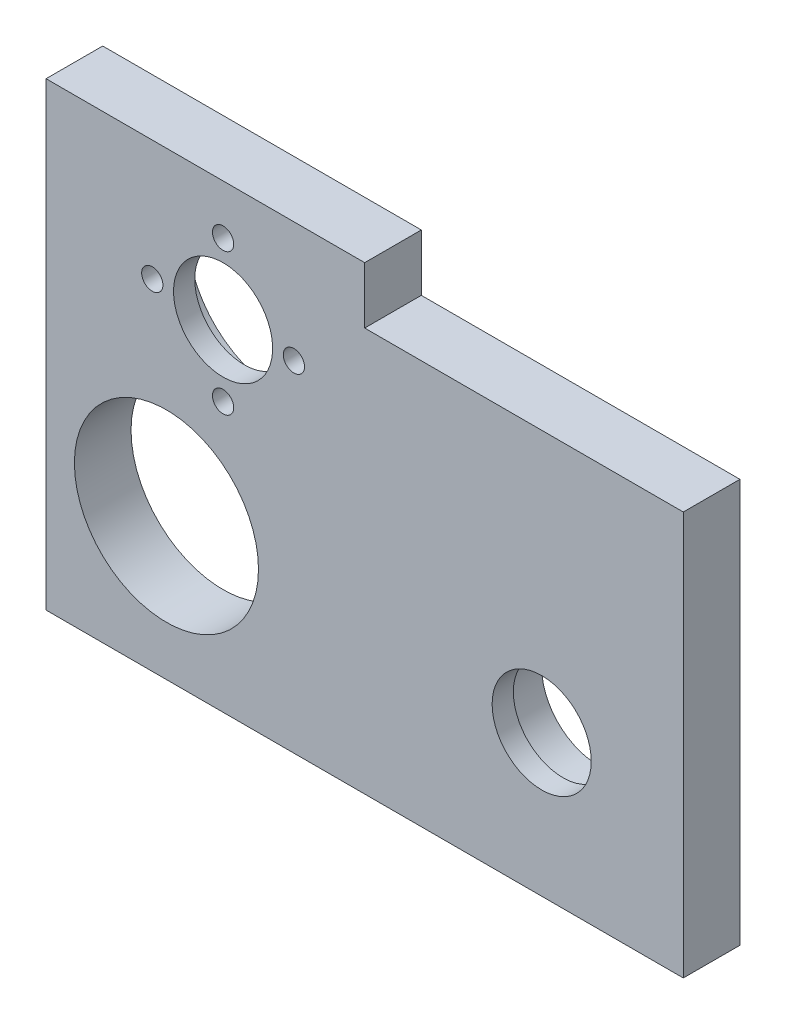
SolidWorks part; units mm, degrees
ref_plane "Front" through (0, 0, 0) normal (0, 0, 1) x (1, 0, 0)
ref_plane "Top" through (0, 0, 0) normal (0, 1, 0) x (1, 0, 0)
ref_plane "Right" through (0, 0, 0) normal (1, 0, 0) x (0, 0, -1)
sketch "Esquisse1" plane through (0, 0, 0) normal (0, 0, 1) x (1, 0, 0)
  line L1 (0, 0) -> (90, 0)
  line L2 (0, 0) -> (0, 65)
  line L3 (0, 65) -> (90, 65)
  line L4 (90, 0) -> (90, 65)
  circle A0 centre (70, 20) radius 7
  circle A1 centre (17, 20) radius 13
  circle A2 centre (25, 48) radius 13
  dimension "D3" = 14
  dimension "D4" = 20
  dimension "D6" = 53
  dimension "D8" = 26
  dimension "D9" = 26
  dimension "D1" = 90
  dimension "D2" = 65
  dimension "D5" = 70
  dimension "D7" = 20
  dimension "D10" = 53
  dimension "D11" = 48
extrude "Boss.-Extru.1" add sketch "Esquisse1" along normal blind 8
sketch "Esquisse2" plane through (0, 0, 0) normal (0, 0, -1) x (-1, 0, 0)
  circle A0 centre (-25, 48) radius 13
  circle A1 centre (-17, 20) radius 13 construction
extrude "Boss.-Extru.2" add sketch "Esquisse2" along normal blind 3 from surface starting at face at (45, 32.5, 8)
sketch "Esquisse3" plane through (0, 0, 5) normal (0, 0, -1) x (-1, 0, 0)
  line L0 (-15, 48) -> (-25, 48) construction
  circle A0 centre (-25, 48) radius 7
  circle A1 centre (-15, 48) radius 1.5
  circle A2 centre (-25, 38) radius 1.5
  circle A3 centre (-35, 48) radius 1.5
  circle A4 centre (-25, 58) radius 1.5
  point P13 (-25, 48)
  dimension "D1" = 14
  dimension "D2" = 3
  dimension "D3" = 10
  dimension "D4" = 4
extrude "Enlèv. mat.-Extru.1" cut sketch "Esquisse3" against normal through all
sketch "Esquisse4" plane through (0, 0, 8) normal (0, 0, 1) x (1, 0, 0)
  circle A0 centre (70, 20) radius 8
  dimension "D1" = 16
extrude "Enlèv. mat.-Extru.2" cut sketch "Esquisse4" along normal blind 5 from surface starting at face at (30, 20, 0)
sketch "Esquisse5" plane through (0, 0, 0) normal (0, 0, -1) x (-1, 0, 0)
  line L1 (-90, 65) -> (-45, 65)
  line L2 (-90, 65) -> (-90, 57)
  line L3 (-90, 57) -> (-45, 57)
  line L4 (-45, 65) -> (-45, 57)
  dimension "D1" = 8
  dimension "D2" = 45
extrude "Enlèv. mat.-Extru.3" cut sketch "Esquisse5" against normal through all
sketch "Esquisse6" plane through (0, 0, 0) normal (-1, 0, 0) x (0, 0, 1)
  line L0 (4, 0) -> (4, 35) construction
  line L1 (8, 0) -> (0, 0) construction
  circle A0 centre (4, 35) radius 1.65
  circle A1 centre (4, 7) radius 1.65
  dimension "D1" = 3.3
  dimension "D2" = 28
  dimension "D3" = 7
extrude "Enlèv. mat.-Extru.4" cut sketch "Esquisse6" against normal blind 10
